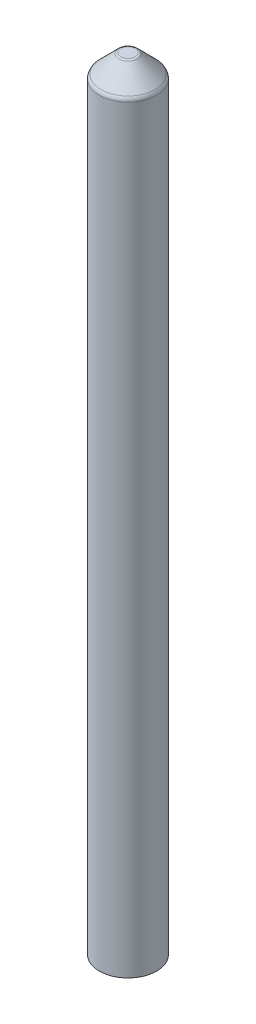
SolidWorks part; units mm, degrees
ref_plane "Front Plane" through (0, 0, 0) normal (0, 0, 1) x (1, 0, 0)
ref_plane "Top Plane" through (0, 0, 0) normal (0, 1, 0) x (1, 0, 0)
ref_plane "Right Plane" through (0, 0, 0) normal (1, 0, 0) x (0, 0, -1)
sketch "Sketch1" plane through (0, 0, 0) normal (0, 1, 0) x (1, 0, 0)
  circle A0 centre (0, 0) radius 25.146
  dimension "D1" = 50.292
extrude "Boss-Extrude2" add sketch "Sketch1" along normal blind 685.8
sketch "Sketch3" plane through (0, 0, 0) normal (0, 0, 1) x (1, 0, 0)
  circle A0 centre (0, 25.4) radius 6.35
  circle A1 centre (0, 154.94) radius 6.35
  circle A2 centre (0, 284.48) radius 6.35
  circle A3 centre (0, 414.02) radius 6.35
  circle A4 centre (0, 543.56) radius 6.35
  point P0 (0, 0)
  dimension "D12" = 12.7
  dimension "D13" = 12.7
  dimension "D14" = 12.7
  dimension "D15" = 12.7
  dimension "D16" = 12.7
extrude "Cut-Extrude2" cut sketch "Sketch3" against normal blind 73.914
chamfer "Chamfer3" distance 17.78 angle 45 1 edges at (0, 685.8, 25.146)
fillet "Fillet8" radius 2.54 1 edges at (0, 685.8, 7.366)
fillet "Fillet9" radius 5.08 1 edges at (0, 668.02, 25.146)
fillet "Fillet10" radius 5.08 5 edges at (1.2376, 19.1718, -25.1155) (1.2376, 148.7118, -25.1155) (1.2376, 278.2518, -25.1155) (1.2376, 407.7918, -25.1155) (1.2376, 537.3318, -25.1155)
